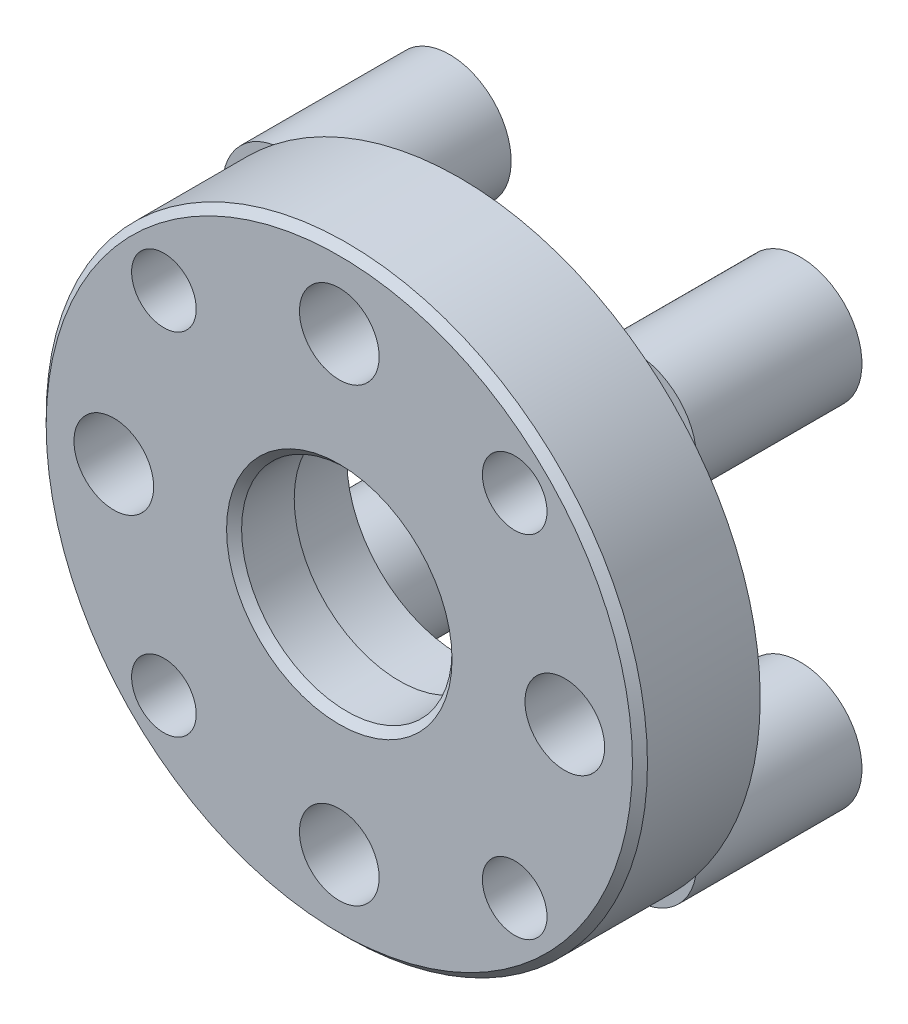
SolidWorks part; units mm, degrees
material "ABS"
ref_plane "Front Plane" through (0, 0, 0) normal (0, 0, 1) x (1, 0, 0)
ref_plane "Top Plane" through (0, 0, 0) normal (0, 1, 0) x (1, 0, 0)
ref_plane "Right Plane" through (0, 0, 0) normal (1, 0, 0) x (0, 0, -1)
ref_plane "Output Plane" through (0, 0, 21.5247) normal (0, 0, -1) x (-1, 0, 0)
sketch "CYC Output Sketch" plane through (0, 0, 21.5247) normal (0, 0, 1) x (1, 0, 0)
  line L1 (11.6673, 11.6673) -> (-11.6673, 11.6673) construction
  line L2 (-11.6673, 11.6673) -> (-11.6673, -11.6673) construction
  line L3 (-11.6673, -11.6673) -> (11.6673, -11.6673) construction
  line L4 (11.6673, -11.6673) -> (11.6673, 11.6673) construction
  circle A0 centre (0, 0) radius 16.5 construction
sketch "Sketch3" plane through (0, 0, 21.5247) normal (0, 0, -1) x (-1, 0, 0)
  circle A0 centre (-11.6673, 11.6673) radius 4
  circle A1 centre (11.6673, 11.6673) radius 4
  circle A2 centre (11.6673, -11.6673) radius 4
  circle A3 centre (-11.6673, -11.6673) radius 4
  dimension "D1" = 8
extrude "Boss-Extrude1" add sketch "Sketch3" along normal blind 11
sketch "Sketch6" plane through (0, 0, 21.5247) normal (0, 0, 1) x (1, 0, 0)
  arc A0 (10.6823, 16.9082) -> (-16.9082, 10.6823) centre (0, 0) ccw
  arc A18 (16.9082, -10.6823) -> (10.6823, 16.9082) centre (0, 0) ccw
  arc A19 (-10.6823, -16.9082) -> (16.9082, -10.6823) centre (0, 0) ccw
  arc A20 (-16.9082, 10.6823) -> (-10.6823, -16.9082) centre (0, 0) ccw
  circle A23 centre (0, 0) radius 7.5
  dimension "D2" = 40
  dimension "D1" = 15
extrude "Boss-Extrude6" add sketch "Sketch6" along normal blind 8 contours A23 | A0 A20 A19 A18 region at (0, 0, 21.5247)
sketch "Sketch8" plane through (0, 0, 29.5247) normal (0, 0, 1) x (1, 0, 0)
  line L0 (0, 0) -> (11.6673, 11.6673) construction
  line L1 (0, 0) -> (16.5, 0) construction
  circle A0 centre (0, 0) radius 16.5 construction
  circle A1 centre (11.6673, 11.6673) radius 1.6
  circle A2 centre (11.6673, -11.6673) radius 1.6
  circle A3 centre (-11.6673, -11.6673) radius 1.6
  circle A4 centre (-11.6673, 11.6673) radius 1.6
  point P16 (0, 0)
  dimension "D1" = 33
  dimension "D2" = 45
  dimension "D3" = 3.2
  dimension "D4" = 4
extrude "Cut-Extrude1" cut sketch "Sketch8" against normal through all
sketch "Sketch9" plane through (0, 0, 10.5247) normal (0, 0, 1) x (1, 0, 0)
  circle A0 centre (11.6673, 11.6673) radius 3
  circle A1 centre (11.6673, -11.6673) radius 3
  circle A2 centre (-11.6673, -11.6673) radius 3
  circle A3 centre (-11.6673, 11.6673) radius 3
  point P12 (0, 0)
  dimension "D1" = 6
  dimension "D2" = 4
extrude "Cut-Extrude2" cut sketch "Sketch9" along normal blind 3 from surface starting at face at (13.2673, 11.6673, 10.5247)
sketch "Sketch10" plane through (0, 0, 10.5247) normal (0, 0, -1) x (-1, 0, 0)
  circle A0 centre (11.6673, 11.6673) radius 4.1
  circle A1 centre (11.6673, 11.6673) radius 4
  circle A2 centre (11.6673, -11.6673) radius 4
  circle A3 centre (11.6673, -11.6673) radius 4.1
  circle A4 centre (-11.6673, -11.6673) radius 4
  circle A5 centre (-11.6673, -11.6673) radius 4.1
  circle A6 centre (-11.6673, 11.6673) radius 4
  circle A7 centre (-11.6673, 11.6673) radius 4.1
  point P16 (0, 0)
  dimension "D1" = 8
  dimension "D2" = 8.2
  dimension "D3" = 4
extrude "Boss-Extrude8" add sketch "Sketch10" against normal blind 11
sketch "Sketch11" plane through (0, 0, 29.5247) normal (0, 0, 1) x (1, 0, 0)
  line L0 (0, 0) -> (0, 15) construction
  circle A0 centre (0, 15) radius 2.65
  circle A1 centre (15, 0) radius 2.65
  circle A2 centre (0, -15) radius 2.65
  circle A3 centre (-15, 0) radius 2.65
  circle A4 centre (-11.6673, 11.6673) radius 2.15
  circle A5 centre (11.6673, 11.6673) radius 2.15
  circle A6 centre (11.6673, -11.6673) radius 2.15
  circle A7 centre (-11.6673, -11.6673) radius 2.15
  point P13 (0, 0)
  dimension "D2" = 5.3
  dimension "D4" = 4.3
  dimension "D1" = 15
  dimension "D3" = 4
extrude "Cut-Extrude3" cut sketch "Sketch11" against normal blind 8
sketch "Sketch12" plane through (0, 0, 29.5247) normal (0, 0, 1) x (1, 0, 0)
  circle A0 centre (0, 0) radius 7.5
  circle A1 centre (0, 0) radius 7
  dimension "D1" = 15
  dimension "D2" = 14
extrude "Boss-Extrude9" add sketch "Sketch12" against normal blind 4
chamfer "Chamfer1" distance 0.5 angle 45 2 edges at (7, 0, 29.5247) (20, 0, 29.5247)
equation "\"RingPinShaft\"= 5.05"
equation "\"CenterBearingOut\"=32.00"
equation "\"RingPostIn\"=5.15"
equation "\"CamBearingOut\"=15.1"
equation "\"DiskOutputShaft\"=10.1"
equation "\"CenterShaft\"=25.2"
equation "\"Eccentricity\"=2"
equation "\"CycCamShaft\"=10.05"
equation "\"D2@Sketch6\"=\"OutputBearing\""
equation "\"OutputBearing\"=40"
